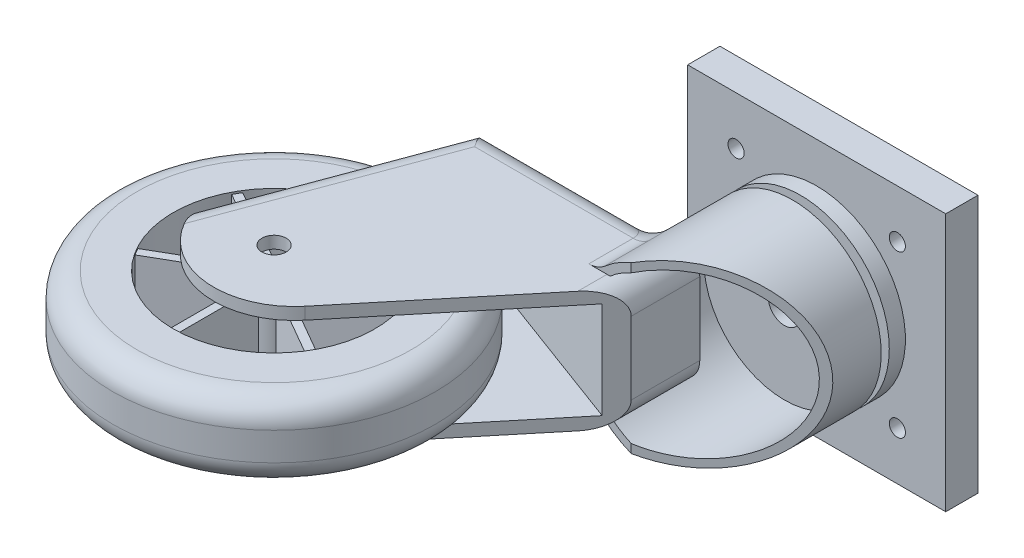
SolidWorks part; units mm, degrees
ref_plane "前视基准面" through (0, 0, 0) normal (0, 0, 1) x (1, 0, 0)
ref_plane "上视基准面" through (0, 0, 0) normal (0, 1, 0) x (1, 0, 0)
ref_plane "右视基准面" through (0, 0, 0) normal (1, 0, 0) x (0, 0, -1)
sketch "草图1" plane through (0, 0, 0) normal (0, 0, 1) x (1, 0, 0)
  line L1 (-15, -15) -> (15, -15)
  line L2 (-15, -15) -> (-15, 15)
  line L3 (-15, 15) -> (15, 15)
  line L4 (15, -15) -> (15, 15)
  line L5 (0, 15) -> (0, -15) construction
  line L6 (-15, 0) -> (15, 0) construction
  circle A0 centre (10, 10) radius 2
  circle A1 centre (10, -10) radius 2
  circle A2 centre (-10, -10) radius 2
  circle A3 centre (-10, 10) radius 2
  point P0 (0, 0)
  dimension "D3" = 4
  dimension "D1" = 30
  dimension "D2" = 30
  dimension "D4" = 5
  dimension "D5" = 5
extrude "凸台-拉伸1" add sketch "草图1" along normal blind 2
sketch "草图2" plane through (0, 0, 2) normal (0, 0, 1) x (1, 0, 0)
  circle A0 centre (0, 0) radius 10
  dimension "D1" = 20
extrude "凸台-拉伸2" add sketch "草图2" along normal blind 2
sketch "草图3" plane through (0, 0, 4) normal (0, 0, 1) x (1, 0, 0)
  circle A0 centre (0, 0) radius 2
  dimension "D1" = 4
extrude "凸台-拉伸3" add sketch "草图3" along normal blind 3
sketch "草图4" plane through (0, 0, 7) normal (0, 0, 1) x (1, 0, 0)
  circle A0 centre (0, 0) radius 10
  dimension "D1" = 20
extrude "凸台-拉伸4" add sketch "草图4" along normal blind 15
shell "抽壳1" thickness 1 removed face at (10, 0, 22) outward yes
sketch "草图5" plane through (0, 0, 0) normal (0, 1, 0) x (1, 0, 0)
  line L0 (-4, -22) -> (11, -22)
  line L1 (-11, -22) -> (11, -22) construction
  line L2 (11, -22) -> (11, -12)
  line L3 (11, -22) -> (11, -6) construction
  line L4 (11, -12) -> (-4, -22)
  dimension "D1" = 10
  dimension "D2" = 15
extrude "切除-拉伸1" cut sketch "草图5" against normal through all both and the other way through all
sketch "草图6" plane through (0, 0, 0) normal (0, 1, 0) x (1, 0, 0)
  line L0 (-4, -22) -> (-4, -13.5)
  line L1 (-4, -13.5) -> (-31, -13.5)
  line L2 (-11, -6) -> (-11, -22) construction
  line L3 (11, -6) -> (-11, -6) construction
  line L4 (-4, -22) -> (-22.2907, -44.1392)
  line L5 (-31, -13.5) -> (-40, -37.77)
  arc A0 (-40, -37.77) -> (-22.2907, -44.1392) centre (-30, -37.77) ccw
  dimension "D1" = 24.27
  dimension "D2" = 20
  dimension "D3" = 19
  dimension "D4" = 20
  dimension "D5" = 7.5
extrude "凸台-拉伸5" add sketch "草图6" along normal blind 15 from offset 7.5 offset against normal yes
sketch "草图7" plane through (-22.8514, 0, -8.474) normal (-0.9376, 0, -0.3477) x (-0.3477, 0, 0.9376)
  line L0 (-1000, 0) -> (49000, 0) construction
  line L1 (24.4362, 6) -> (68.3462, 6)
  line L2 (24.4362, 6) -> (24.4362, -6)
  line L3 (24.4362, -6) -> (68.3462, -6)
  line L4 (68.3462, 6) -> (68.3462, -6)
  line L5 (23.4362, 7.5) -> (23.4362, -7.5) construction
  dimension "D1" = 43.91
  dimension "D2" = 12
  dimension "D3" = 1
extrude "切除-拉伸2" cut sketch "草图7" against normal through all
sketch "草图8" plane through (0, 7.5, 0) normal (0, 1, 0) x (1, 0, 0)
  circle A0 centre (-30.7837, -39.5) radius 1.5
  point P4 (-29.1079, -39.5)
  point P5 (0, 0)
  point P6 (0, 0)
  dimension "D2" = 3
extrude "切除-拉伸3" cut sketch "草图8" against normal through all
sketch "草图11" plane through (0, 0, 0) normal (0, 1, 0) x (1, 0, 0)
  line L0 (-30.7837, -1039.5) -> (-30.7837, -42) construction
  line L1 (-30.7837, -37) -> (-30.7837, -27) construction
  line L3 (-31.2837, -37.0505) -> (-31.2837, -27.01)
  line L5 (-30.2837, -37.0505) -> (-30.2837, -27.01)
  line L6 (-30.7837, -27) -> (-30.7837, -37) construction
  line L7 (-31.2837, -32.0303) -> (-30.2837, -32.0303) construction
  line L8 (-30.7837, -23.2215) -> (-30.7837, 48960.5) construction
  line L9 (-28.9124, -37.8422) -> (-20.2171, -32.822)
  line L10 (-28.4124, -38.7083) -> (-19.7171, -33.688)
  line L11 (-28.4124, -40.2917) -> (-19.7171, -45.312)
  line L12 (-28.9124, -41.1578) -> (-20.2171, -46.178)
  line L13 (-30.2837, -41.9495) -> (-30.2837, -51.99)
  line L14 (-31.2837, -41.9495) -> (-31.2837, -51.99)
  line L15 (-32.655, -41.1578) -> (-41.3504, -46.178)
  line L16 (-33.155, -40.2917) -> (-41.8504, -45.312)
  line L17 (-33.155, -38.7083) -> (-41.8504, -33.688)
  line L18 (-32.655, -37.8422) -> (-41.3504, -32.822)
  arc A0 (-33.155, -38.7083) -> (-33.155, -40.2917) centre (-30.7837, -39.5) ccw
  arc A1 (-41.3504, -32.822) -> (-41.8504, -33.688) centre (-30.7837, -39.5) ccw
  arc A2 (-32.655, -41.1578) -> (-31.2837, -41.9495) centre (-30.7837, -39.5) ccw
  arc A3 (-30.2837, -41.9495) -> (-28.9124, -41.1578) centre (-30.7837, -39.5) ccw
  arc A4 (-28.9124, -37.8422) -> (-30.2837, -37.0505) centre (-30.7837, -39.5) ccw
  arc A5 (-28.4124, -40.2917) -> (-28.4124, -38.7083) centre (-30.7837, -39.5) ccw
  arc A6 (-30.2837, -27.01) -> (-31.2837, -27.01) centre (-30.7837, -39.5) ccw
  arc A7 (-19.7171, -33.688) -> (-20.2171, -32.822) centre (-30.7837, -39.5) ccw
  arc A8 (-20.2171, -46.178) -> (-19.7171, -45.312) centre (-30.7837, -39.5) ccw
  arc A9 (-31.2837, -51.99) -> (-30.2837, -51.99) centre (-30.7837, -39.5) ccw
  arc A10 (-41.8504, -45.312) -> (-41.3504, -46.178) centre (-30.7837, -39.5) ccw
  arc A11 (-31.2837, -37.0505) -> (-32.655, -37.8422) centre (-30.7837, -39.5) ccw
  point P3 (-30.7837, -32.0303)
  point P38 (-30.7837, -39.5)
  dimension "D1" = 25
  dimension "D2" = 5
  dimension "D3" = 1
  dimension "D4" = 6
extrude "凸台-拉伸6" add sketch "草图11" along normal mid plane 9 separate body
sketch "草图12" plane through (0, 0, 0) normal (0, 1, 0) x (1, 0, 0)
  circle A0 centre (-30.7837, -39.5) radius 12.5
  circle A1 centre (-30.7837, -39.5) radius 20
  dimension "D1" = 25
  dimension "D2" = 40
extrude "凸台-拉伸7" add sketch "草图12" along normal mid plane 9.5
fillet "圆角1" radius 3 7 edges at (-8.0467, 7.5, 17.75) (-8.0467, -7.5, 17.75) (-35.5, -7.5, 25.635) (-35.5, 7.5, 25.635) (-11, 0, 13.5) (-19.5234, -7.5, 13.5) (-19.5234, 7.5, 13.5)
fillet "圆角2" radius 3 2 edges at (-4, 7.5, 17.75) (-4, -7.5, 17.75)
fillet "圆角3" radius 3 2 edges at (-30.7837, 4.75, 59.5) (-30.7837, -4.75, 59.5)
